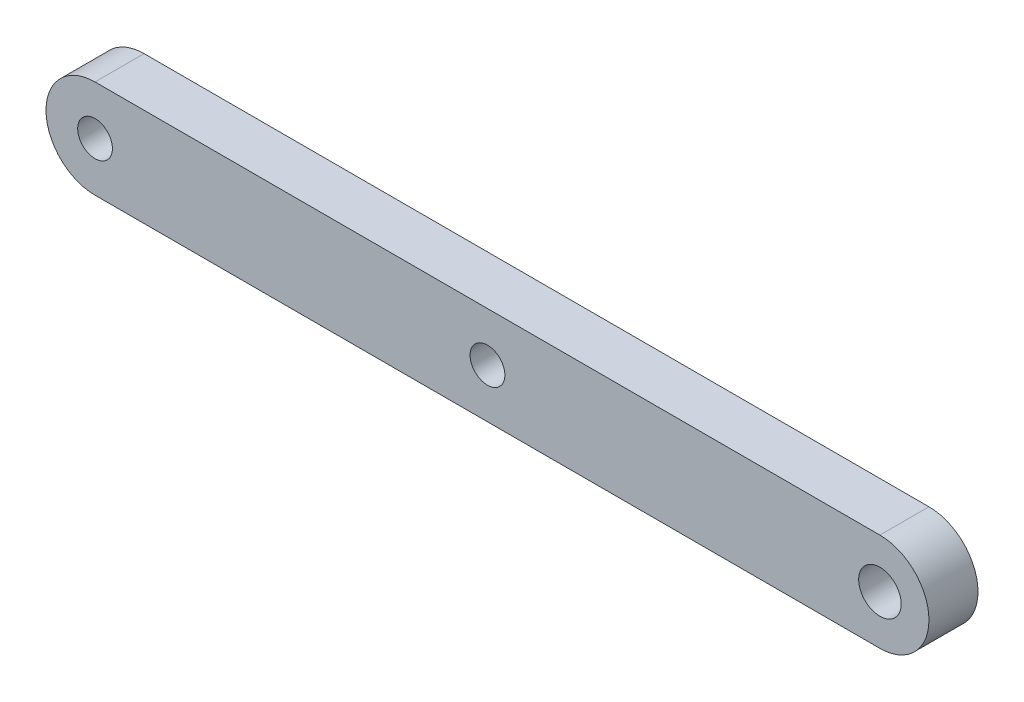
SolidWorks part; units mm, degrees
ref_plane "Front Plane" through (0, 0, 0) normal (0, 0, 1) x (1, 0, 0)
ref_plane "Top Plane" through (0, 0, 0) normal (0, 1, 0) x (1, 0, 0)
ref_plane "Right Plane" through (0, 0, 0) normal (1, 0, 0) x (0, 0, -1)
sketch "Sketch1" plane through (0, 0, 0) normal (0, 0, 1) x (1, 0, 0)
  line L0 (0, 0) -> (101.6, 0) construction
  line L1 (0, 6.35) -> (101.6, 6.35)
  line L2 (0, -6.35) -> (101.6, -6.35)
  arc A0 (0, 6.35) -> (0, -6.35) centre (0, 0) ccw
  arc A1 (101.6, -6.35) -> (101.6, 6.35) centre (101.6, 0) ccw
  circle A2 centre (101.6, 0) radius 2.575 construction
  circle A3 centre (50.8, 0) radius 2.0625 construction
  point P3 (50.8, 0)
  dimension "D2" = 6.35
  dimension "D3" = 5.15
  dimension "D4" = 4.125
  dimension "D1" = 101.6
extrude "Boss-Extrude1" add sketch "Sketch1" along normal blind 6.35
sketch "Sketch2" plane through (0, 0, 6.35) normal (0, 0, 1) x (1, 0, 0)
  line L0 (0, 0) -> (101.6, 0) construction
  line L1 (-1.3843, 0.4953) -> (1.3843, 0.4953)
  line L2 (-1.3843, 0.4953) -> (-1.3843, -0.4953)
  line L3 (-1.3843, -0.4953) -> (1.3843, -0.4953)
  line L4 (1.3843, 0.4953) -> (1.3843, -0.4953)
  line L5 (0, -0.4953) -> (0, 0.4953) construction
  line L6 (-1.3843, 0) -> (1.3843, 0) construction
  point P88 (0, 0)
  dimension "D1" = 0.9906
  dimension "D2" = 2.7686
extrude "Cut-Extrude1" [suppressed] cut sketch "Sketch2" against normal blind 6.35
hole_wizard "M5 Clearance Hole1" positions "Sketch3" profile "Sketch4" hole size "M5" standard "ANSI Metric" end condition through all
sketch "Sketch3" plane through (0, 0, 0) normal (0, 0, -1) x (-1, 0, 0)
  point P0 (-101.6, 0)
sketch "Sketch4" plane through (101.6, 0, 0) normal (1, 0, 0) x (0, 1, 0)
  line L0 (0, 0) -> (0, 6.35)
  line L1 (0, 6.35) -> (2.75, 6.35)
  line L2 (2.75, 6.35) -> (2.75, 0)
  line L5 (2.75, 0) -> (0, 0)
  line L11 (0, -6.35) -> (0, 107.95) construction
  dimension "Thru Hole Dia." = 5.5
  dimension "Thru Hole Depth" = 6.35
hole_wizard "M4 Clearance Hole1" positions "Sketch5" profile "Sketch6" hole size "M4" standard "ANSI Metric" end condition through all
sketch "Sketch5" plane through (0, 0, 0) normal (0, 0, -1) x (-1, 0, 0)
  point P0 (-50.8, 0)
  point P3 (0, 0)
sketch "Sketch6" plane through (50.8, 0, 0) normal (1, 0, 0) x (0, 1, 0)
  line L0 (0, 0) -> (0, 6.35)
  line L1 (0, 6.35) -> (2.25, 6.35)
  line L2 (2.25, 6.35) -> (2.25, 0)
  line L5 (2.25, 0) -> (0, 0)
  line L11 (0, -6.35) -> (0, 107.95) construction
  dimension "Thru Hole Dia." = 4.5
  dimension "Thru Hole Depth" = 6.35
equation "\"spring width\"= .099in"
equation "\"spring thick\"= .029in"
equation "\"stock thick\"= .25in"
equation "\"D1@Boss-Extrude1\"=\"stock thick\""
equation "\"D1@Sketch2\"=\"spring thick\" + .01"
equation "\"D2@Sketch2\"=\"spring width\" + .01"
equation "\"D1@Cut-Extrude1\"=\"stock thick\""
